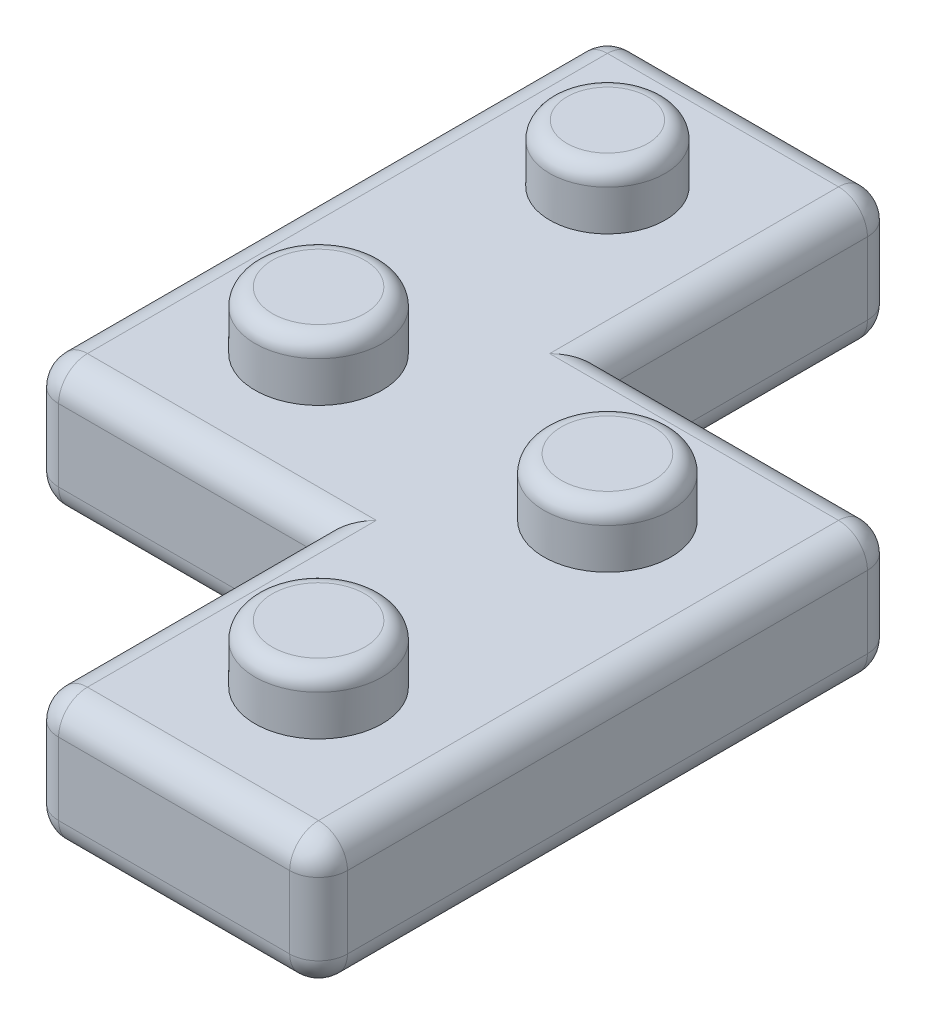
SolidWorks part; units mm, degrees
material "ABS PC"
ref_plane "Front Plane" through (0, 0, 0) normal (0, 0, 1) x (1, 0, 0)
ref_plane "Top Plane" through (0, 0, 0) normal (0, 1, 0) x (1, 0, 0)
ref_plane "Right Plane" through (0, 0, 0) normal (1, 0, 0) x (0, 0, -1)
sketch "Sketch1" plane through (0, 0, 0) normal (0, 1, 0) x (1, 0, 0)
  line L0 (-5.6746, 20.3112) -> (7.0254, 20.3112)
  line L1 (7.0254, 20.3112) -> (7.0254, 7.6112)
  line L2 (7.0254, 7.6112) -> (19.7254, 7.6112)
  line L3 (19.7254, 7.6112) -> (19.7254, -17.7888)
  line L4 (19.7254, -17.7888) -> (7.0254, -17.7888)
  line L5 (7.0254, -17.7888) -> (7.0254, -5.0888)
  line L6 (7.0254, -5.0888) -> (-5.6746, -5.0888)
  line L7 (-5.6746, -5.0888) -> (-5.6746, 20.3112)
  dimension "D1" = 38.1
  dimension "D2" = 12.7
  dimension "D3" = 12.7
  dimension "D4" = 12.7
  dimension "D5" = 12.7
extrude "Boss-Extrude1" add sketch "Sketch1" along normal blind 5.715
sketch "Sketch2" plane through (0, 5.715, 0) normal (0, 1, 0) x (1, 0, 0)
  line L0 (-5.6746, 20.3112) -> (-5.6746, -5.0888) construction
  line L1 (19.7254, -17.7888) -> (19.7254, 7.6112) construction
  line L2 (7.0254, 20.3112) -> (-5.6746, 20.3112) construction
  circle A0 centre (0.6754, 1.2612) radius 2.794
  circle A1 centre (13.3754, 1.2612) radius 2.794
  circle A2 centre (0.6754, 13.9612) radius 2.54
  circle A3 centre (13.3754, -11.4388) radius 2.794
  dimension "D2" = 6.35
  dimension "D4" = 6.35
  dimension "D5" = 12.7
  dimension "D3" = 6.35
  dimension "D6" = 12.7
  dimension "D1" = 2
extrude "Boss-Extrude3" add sketch "Sketch2" along normal blind 2.54
fillet "Fillet1" radius 1.27 21 edges at (19.7254, 2.8575, 17.7888) (7.0254, 0, -13.9612) (0.6754, 0, 5.0888) (13.3754, 0, 17.7888) (19.7254, 0, 5.0888) (7.0254, 5.715, -13.9612) (7.0254, 2.8575, -20.3112) (0.6754, 0, -20.3112) (0.6754, 5.715, -20.3112) (-5.6746, 2.8575, -20.3112) (-5.6746, 5.715, -7.6112) (-5.6746, 2.8575, 5.0888) (0.6754, 5.715, 5.0888) (7.0254, 0, 11.4388) (7.0254, 2.8575, 17.7888) (7.0254, 5.715, 11.4388) (13.3754, 5.715, 17.7888) (19.7254, 5.715, 5.0888) (13.3754, 5.715, -7.6112) (13.3754, 0, -7.6112) (19.7254, 2.8575, -7.6112)
fillet "Fillet2" radius 1.27 3 edges at (-5.3026, 0.372, -19.9392) (-5.3026, 0.372, 4.7168) (-5.6746, 0, -7.6112)
fillet "Fillet3" radius 0.762 4 edges at (13.3754, 8.255, 1.5328) (13.3754, 8.255, 14.2328) (0.6754, 8.255, -11.4212) (0.6754, 8.255, 1.5328)
